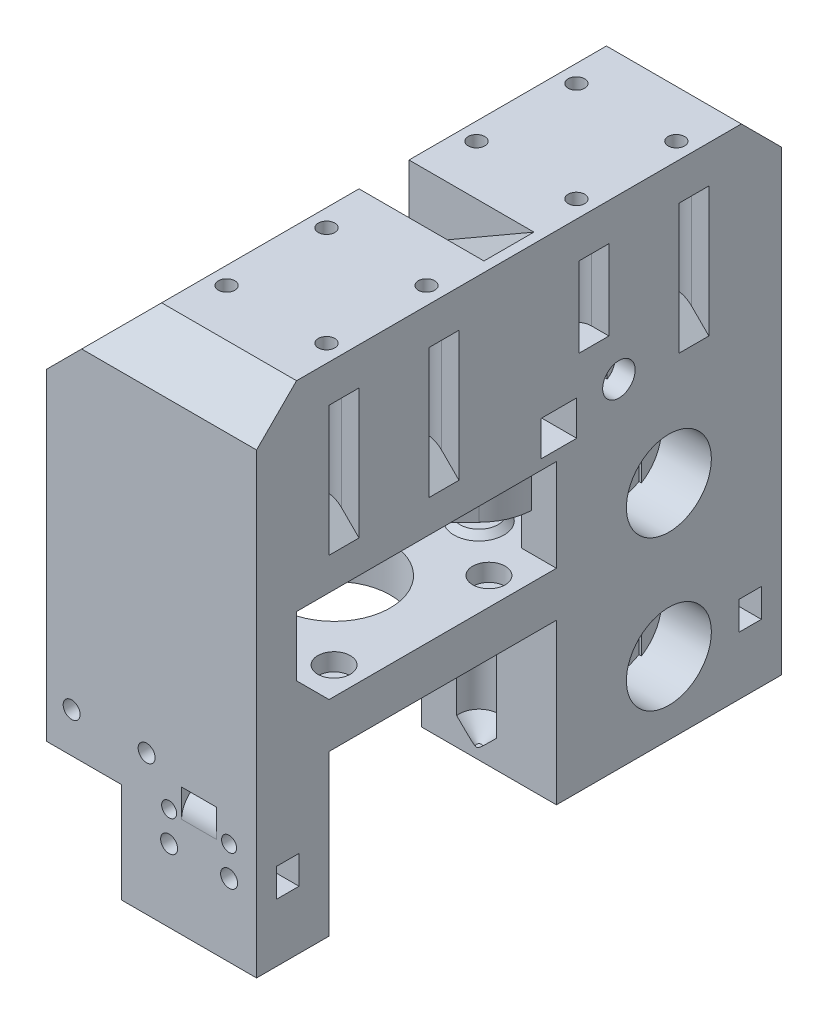
SolidWorks part; units mm, degrees
material "3D printed plastic"
ref_plane "Front Plane" through (0, 0, 0) normal (0, 0, 1) x (1, 0, 0)
ref_plane "Top Plane" through (0, 0, 0) normal (0, 1, 0) x (1, 0, 0)
ref_plane "Right Plane" through (0, 0, 0) normal (1, 0, 0) x (0, 0, -1)
sketch "Sketch1" plane through (0, 0, 0) normal (0, 1, 0) x (1, 0, 0)
  line L0 (-13.5, 52.5) -> (13.5, -52.5) construction
  line L1 (-13.5, 52.5) -> (13.5, 52.5)
  line L2 (-13.5, 52.5) -> (-13.5, -52.5)
  line L3 (-13.5, -52.5) -> (13.5, -52.5)
  line L4 (13.5, 52.5) -> (13.5, -52.5)
  dimension "D1" = 27
  dimension "D2" = 105
extrude "Boss-Extrude1" add sketch "Sketch1" against normal blind 40
sketch "Sketch2" plane through (0, -40, 0) normal (0, -1, 0) x (-1, 0, 0)
  line L0 (-13.5, -52.5) -> (-13.5, 52.5) construction
  line L1 (13.5, 52.5) -> (-13.5, 52.5)
  line L2 (13.5, 52.5) -> (13.5, 45.1)
  line L3 (13.5, 7.5) -> (-13.5, 7.5)
  line L4 (-13.5, 52.5) -> (-13.5, 7.5)
  line L5 (13.5, 14.9) -> (13.5, 7.5)
  line L6 (13.5, 45.1) -> (8.5, 45.1)
  line L7 (8.5, 30) -> (13.5, 30) construction
  line L8 (13.5, 14.9) -> (8.5, 14.9)
  line L9 (8.5, 45.1) -> (8.5, 14.9)
  line L10 (13.5, 52.5) -> (13.5, -52.5) construction
  dimension "D1" = 30.2
  dimension "D2" = 22.5
  dimension "D3" = 5
  dimension "D4" = 45
extrude "Boss-Extrude2" add sketch "Sketch2" along normal blind 59.5
sketch "Sketch4" plane through (13.5, 0, 0) normal (1, 0, 0) x (0, 0, -1)
  line L0 (30, -55) -> (30, -85) construction
  line L1 (30, -85) -> (30, -99.5) construction
  line L2 (45.1, -99.5) -> (14.9, -99.5) construction
  line L3 (14.9, -40) -> (45.1, -40) construction
  circle A0 centre (30, -85) radius 4.5
  circle A1 centre (30, -55) radius 4.5
  dimension "D1" = 30
  dimension "D3" = 9
  dimension "D2" = 15
extrude "Cut-Extrude2" cut sketch "Sketch4" against normal through all
sketch "Sketch5" plane through (13.5, 0, 0) normal (1, 0, 0) x (0, 0, -1)
  circle A0 centre (30, -85) radius 8.5
  circle A1 centre (30, -55) radius 8.5
  dimension "D1" = 17
extrude "Cut-Extrude3" cut sketch "Sketch5" against normal blind 10
sketch "Sketch6" plane through (0, 0, 0) normal (0, 1, 0) x (-1, 0, 0)
  line L0 (-10, 35) -> (-10, 15) construction
  line L1 (-10, 15) -> (10, 15) construction
  line L2 (10, 15) -> (10, 35) construction
  line L3 (10, 35) -> (-10, 35) construction
  line L5 (-10, 35) -> (10, 15) construction
  line L6 (0, 25) -> (0, -25) construction
  line L7 (0, 0) -> (13.5, 0) construction
  line L8 (-10, -35) -> (10, -15) construction
  line L9 (10, -35) -> (-10, -35) construction
  line L10 (10, -15) -> (10, -35) construction
  line L11 (-10, -15) -> (10, -15) construction
  line L12 (-10, -35) -> (-10, -15) construction
  line L13 (13.5, -52.5) -> (13.5, 52.5) construction
  circle A0 centre (-10, 35) radius 1.65
  circle A1 centre (10, 35) radius 1.65
  circle A2 centre (10, 15) radius 1.65
  circle A3 centre (-10, 15) radius 1.65
  circle A4 centre (-10, -15) radius 1.65
  circle A5 centre (10, -15) radius 1.65
  circle A6 centre (10, -35) radius 1.65
  circle A7 centre (-10, -35) radius 1.65
  dimension "D1" = 20
  dimension "D2" = 3.3
  dimension "D3" = 50
  dimension "D4" = 13.5
extrude "Cut-Extrude4" cut sketch "Sketch6" against normal blind 10
ref_plane "Plane2" through (0, -67.5, 0) normal (0, -1, 0) x (-1, 0, 0)
sketch "Sketch10" plane through (0, -67.5, 0) normal (0, -1, 0) x (-1, 0, 0)
  line L0 (-8, -0.5) -> (23, -0.5) construction
  line L1 (-13.5, 52.5) -> (-13.5, 7.5) construction
  line L2 (28.5, 7.5) -> (28.5, -38)
  line L3 (28.5, -38) -> (-13.5, -38)
  line L4 (-13.5, -5.9608) -> (-13.5, -38)
  line L5 (23, -0.5) -> (23, -31.5) construction
  line L6 (23, -31.5) -> (-8, -31.5) construction
  line L7 (-8, -31.5) -> (-8, -0.5) construction
  line L8 (-8, -0.5) -> (23, -31.5) construction
  line L9 (7.5, -16) -> (28.5, -16) construction
  line L10 (13.5, 14.9) -> (13.5, 7.5)
  line L11 (13.5, 14.9) -> (-13.5, 14.9)
  line L12 (13.5, 7.5) -> (28.5, 7.5)
  line L14 (-13.5, 14.9) -> (-13.5, -5.9608)
  circle A0 centre (7.5, -16) radius 11.25
  circle A1 centre (23, -0.5) radius 1.75 construction
  circle A2 centre (23, -31.5) radius 1.75
  circle A3 centre (-8, -31.5) radius 1.75
  circle A4 centre (-8, -0.5) radius 1.75
  dimension "D1" = 31
  dimension "D2" = 22.5
  dimension "D3" = 3.5
  dimension "D4" = 22
  dimension "D5" = 21
  dimension "D6" = 42
  dimension "D7" = 23.5
extrude "Boss-Extrude3" add sketch "Sketch10" against normal blind 9
sketch "Sketch11" plane through (13.5, 0, 0) normal (1, 0, 0) x (0, 0, -1)
  line L0 (52.5, -99.5) -> (7.5, -99.5) construction
  line L1 (-38, -99.5) -> (-52.5, -99.5)
  line L2 (-38, -99.5) -> (-38, -58.5)
  line L3 (-44.5, 0) -> (-52.5, 0)
  line L4 (-52.5, -99.5) -> (-52.5, 0)
  line L6 (-38, -58.5) -> (-44.5, -52)
  line L8 (-44.5, -52) -> (-44.5, 0)
  dimension "D1" = 8
  dimension "D2" = 45
extrude "Boss-Extrude4" add sketch "Sketch11" against normal up to surface (42 mm away) up to face at (-28.5, -63, 15.25)
sketch "Sketch24" plane through (0, -58.5, 0) normal (0, 1, 0) x (-1, 0, 0)
  circle A0 centre (21.5, 6.5) radius 2.1
  circle A1 centre (2.5, -8) radius 2.1
  circle A2 centre (7.5, 16) radius 11.25 construction
  dimension "D1" = 4.2
  dimension "D2" = 9.5
  dimension "D4" = 14
  dimension "D5" = 5
  dimension "D3" = 24
extrude "Cut-Extrude16" cut sketch "Sketch24" against normal blind 15
sketch "Sketch26" plane through (0, -58.5, 0) normal (0, 1, 0) x (-1, 0, 0)
  line L0 (2.5, -17) -> (13.5, -17)
  line L1 (13.5, -17) -> (13.5, 1)
  line L2 (13.5, 1) -> (2.5, 1)
  line L4 (13.5, -52.5) -> (13.5, 44.5) construction
  arc A0 (2.5, 1) -> (2.5, -17) centre (2.5, -8) ccw
  dimension "D1" = 18
extrude "Cut-Extrude18" cut sketch "Sketch26" along normal blind 7.5
sketch "Sketch27" plane through (0, -67.5, 0) normal (0, -1, 0) x (-1, 0, 0)
  circle A0 centre (2.5, 8) radius 4
  circle A1 centre (21.5, -6.5) radius 4
  dimension "D1" = 8
extrude "Cut-Extrude19" cut sketch "Sketch27" against normal blind 4.5 and the other way blind 30
sketch "Sketch28" plane through (0, -51, 0) normal (0, -1, 0) x (-1, 0, 0)
  line L0 (21.5, -12) -> (9.0147, -12)
  line L1 (5.4792, -10.5355) -> (-5.2782, 0.2218)
  line L2 (21.5, -1) -> (14.5, -1)
  line L3 (13.5, 0) -> (13.5, 8)
  line L4 (13.5, 14.9) -> (13.5, 7.5) construction
  line L5 (11.0668, 14.9) -> (8.5, 14.9)
  line L6 (8.5, 14.9) -> (8.5, 17.2195)
  line L8 (8.5, 14.9) -> (13.5, 14.9) construction
  arc A0 (13.5, 8) -> (11.0668, 14.9) centre (2.5, 8) ccw
  arc A1 (8.5, 17.2195) -> (-5.2782, 0.2218) centre (2.5, 8) ccw
  arc A2 (21.5, -12) -> (21.5, -1) centre (21.5, -6.5) ccw
  arc A3 (9.0147, -12) -> (5.4792, -10.5355) centre (9.0147, -7) cw
  arc A4 (14.5, -1) -> (13.5, 0) centre (14.5, 0) cw
  arc A5 (2.5, 17) -> (-6.4861, 7.5) centre (2.5, 8) ccw construction
  dimension "D1" = 45
  dimension "D2" = 11
  dimension "D3" = 5
  dimension "D4" = 1
extrude "Boss-Extrude6" add sketch "Sketch28" against normal blind 20
sketch "Sketch29" plane through (0, -51, 0) normal (0, -1, 0) x (-1, 0, 0)
  circle A0 centre (2.5, 8) radius 2.1
  circle A2 centre (21.5, -6.5) radius 2.1
  circle A3 centre (21.5, -6.5) radius 2.1 construction
extrude "Cut-Extrude20" cut sketch "Sketch29" against normal blind 20
sketch "Sketch30" plane through (0, -58.5, 0) normal (0, 1, 0) x (-1, 0, 0)
  circle A0 centre (2.5, -8) radius 2.1
  circle A1 centre (2.5, -8) radius 5
  circle A2 centre (2.5, -8) radius 2.1 construction
  circle A3 centre (21.5, 6.5) radius 2.1 construction
  circle A4 centre (21.5, 6.5) radius 2.1
  circle A6 centre (21.5, 6.5) radius 5
  dimension "D1" = 10
extrude "Boss-Extrude7" add sketch "Sketch30" along normal blind 1.2
sketch "Sketch31" plane through (0, -51, 0) normal (0, -1, 0) x (-1, 0, 0)
  circle A0 centre (2.5, 8) radius 2.1
  circle A1 centre (2.5, 8) radius 5
  circle A2 centre (2.5, 8) radius 2.1 construction
  circle A3 centre (2.5, 8) radius 5 construction
  circle A4 centre (21.5, -6.5) radius 2.1
  circle A5 centre (21.5, -6.5) radius 2.1 construction
  circle A6 centre (21.5, -6.5) radius 5
extrude "Boss-Extrude8" add sketch "Sketch31" along normal blind 1.2
chamfer "Chamfer6" distance 1.2 angle 45 4 edges at (-21.5, -57.3, 11.5) (-2.5, -57.3, -3) (-2.5, -52.2, -13) (-21.5, -52.2, 1.5)
sketch "Sketch32" plane through (0, -31, 0) normal (0, 1, 0) x (-1, 0, 0)
  line L1 (25.5992, 6.5) -> (23.5496, 10.05)
  line L2 (23.5496, 10.05) -> (19.4504, 10.05)
  line L3 (19.4504, 10.05) -> (17.4008, 6.5)
  line L4 (17.4008, 6.5) -> (19.4504, 2.95)
  line L5 (19.4504, 2.95) -> (23.5496, 2.95)
  line L6 (23.5496, 2.95) -> (25.5992, 6.5)
  line L7 (6.5992, -8) -> (4.5496, -4.45)
  line L8 (4.5496, -4.45) -> (0.4504, -4.45)
  line L9 (0.4504, -4.45) -> (-1.5992, -8)
  line L10 (-1.5992, -8) -> (0.4504, -11.55)
  line L11 (0.4504, -11.55) -> (4.5496, -11.55)
  line L12 (4.5496, -11.55) -> (6.5992, -8)
  circle A0 centre (21.5, 6.5) radius 3.55 construction
  circle A1 centre (2.5, -8) radius 3.55 construction
  dimension "D1" = 7.1
extrude "Cut-Extrude21" cut sketch "Sketch32" against normal blind 7
sketch "Sketch34" plane through (0, -58.5, 0) normal (0, 1, 0) x (-1, 0, 0)
  circle A0 centre (-8, 31.5) radius 3.25
  circle A1 centre (23, 31.5) radius 3.25
  circle A2 centre (-8, 0.5) radius 3.25
  circle A3 centre (-8, 0.5) radius 1.75 construction
  dimension "D1" = 6.5
extrude "Cut-Extrude23" cut sketch "Sketch34" against normal blind 3.5
sketch "Sketch35" plane through (0, -38, 0) normal (0, 1, 0) x (1, 0, 0)
  line L0 (-0.4504, 11.55) -> (13.5, 11.55)
  line L1 (13.5, 11.55) -> (13.5, 4.45)
  line L2 (13.5, 4.45) -> (-0.4504, 4.45)
  line L3 (-0.4504, 4.45) -> (-0.4504, 11.55)
  line L4 (13.5, 7.5) -> (13.5, -38) construction
extrude "Cut-Extrude24" cut sketch "Sketch35" along normal up to surface (7 mm away) up to face at (-2.5, -31, -8)
chamfer "Chamfer7" distance 3.5 angle 45 1 edges at (-2.5, -97.5, -12)
chamfer "Chamfer8" distance 15 angle 45 1 edges at (-28.5, 0, 48.5)
chamfer "Chamfer10" distance 12 angle 45 1 edges at (-13.5, -31, 6)
sketch "Sketch36" plane through (0, 0, 0) normal (0, 1, 0) x (1, 0, 0)
  line L0 (-10, 35) -> (-13.5, 35) construction
  line L1 (-13.5, 52.5) -> (-13.5, -44.5) construction
  line L2 (-10, 32) -> (-13.5, 32)
  line L3 (-10, 38) -> (-13.5, 38)
  line L4 (-10, 15) -> (-13.5, 15) construction
  line L5 (-10, 12) -> (-13.5, 12)
  line L6 (-10, 18) -> (-13.5, 18)
  line L7 (-10, -15) -> (-13.5, -15) construction
  line L8 (-10, -18) -> (-13.5, -18)
  line L9 (-10, -12) -> (-13.5, -12)
  line L10 (-10, -35) -> (-13.5, -35) construction
  line L11 (-10, -38) -> (-13.5, -38)
  line L12 (-10, -32) -> (-13.5, -32)
  line L13 (10, 35) -> (13.5, 35) construction
  line L14 (13.5, -52.5) -> (13.5, 52.5) construction
  line L15 (10, 38) -> (13.5, 38)
  line L16 (10, 32) -> (13.5, 32)
  line L17 (10, 15) -> (13.5, 15) construction
  line L18 (10, 18) -> (13.5, 18)
  line L19 (10, 12) -> (13.5, 12)
  line L20 (10, -15) -> (13.5, -15) construction
  line L21 (10, -12) -> (13.5, -12)
  line L22 (10, -18) -> (13.5, -18)
  line L23 (10, -35) -> (13.5, -35) construction
  line L24 (10, -32) -> (13.5, -32)
  line L25 (10, -38) -> (13.5, -38)
  arc A0 (-10, 32) -> (-10, 38) centre (-10, 35) ccw
  arc A1 (-13.5, 38) -> (-13.5, 32) centre (-13.5, 35) ccw
  arc A2 (-10, 12) -> (-10, 18) centre (-10, 15) ccw
  arc A3 (-13.5, 18) -> (-13.5, 12) centre (-13.5, 15) ccw
  arc A4 (-10, -18) -> (-10, -12) centre (-10, -15) ccw
  arc A5 (-13.5, -12) -> (-13.5, -18) centre (-13.5, -15) ccw
  arc A6 (-10, -38) -> (-10, -32) centre (-10, -35) ccw
  arc A7 (-13.5, -32) -> (-13.5, -38) centre (-13.5, -35) ccw
  circle A8 centre (-10, -15) radius 1.65 construction
  arc A9 (10, 38) -> (10, 32) centre (10, 35) ccw
  arc A10 (13.5, 32) -> (13.5, 38) centre (13.5, 35) ccw
  arc A11 (10, 18) -> (10, 12) centre (10, 15) ccw
  arc A12 (13.5, 12) -> (13.5, 18) centre (13.5, 15) ccw
  arc A13 (10, -12) -> (10, -18) centre (10, -15) ccw
  arc A14 (13.5, -18) -> (13.5, -12) centre (13.5, -15) ccw
  arc A15 (10, -32) -> (10, -38) centre (10, -35) ccw
  arc A16 (13.5, -38) -> (13.5, -32) centre (13.5, -35) ccw
  point P5 (-11.75, 35)
  point P10 (-11.75, 15)
  point P18 (-11.75, -15)
  point P25 (-11.75, -35)
  point P40 (11.75, 35)
  point P45 (11.75, 15)
  point P53 (11.75, -15)
  point P61 (11.75, -35)
  dimension "D1" = 6
extrude "Cut-Extrude25" cut sketch "Sketch36" against normal blind 16 from offset 7.5 offset against normal yes
chamfer "Chamfer12" distance 10 angle 45 6 edges at (-13.5, -23.5, -35) (-13.5, -23.5, 15) (-13.5, -23.5, 35) (13.5, -23.5, -35) (13.5, -23.5, 15) (13.5, -23.5, 35)
sketch "Sketch37" plane through (-13.5, 0, 0) normal (-1, 0, 0) x (0, 0, 1)
  line L1 (-23.8, -40) -> (-16.2, -40)
  line L2 (-23.8, -40) -> (-23.8, -24)
  line L3 (-23.8, -24) -> (-16.2, -24)
  line L4 (-16.2, -40) -> (-16.2, -24)
  line L5 (-20, -40) -> (-20, -55) construction
  line L6 (-30, -55) -> (-20, -55) construction
  line L7 (-23.8, -32) -> (-25.8998, -32) construction
  circle A0 centre (-30, -55) radius 4.5 construction
  dimension "D1" = 10
  dimension "D2" = 7.6
  dimension "D3" = 16
  dimension "D4" = 23
extrude "Cut-Extrude26" cut sketch "Sketch37" against normal blind 20
sketch "Sketch38" plane through (6.5, 0, 0) normal (-1, 0, 0) x (0, 0, 1)
  line L0 (-23.8, -24) -> (-16.2, -40) construction
  circle A0 centre (-20, -32) radius 1.65
  dimension "D1" = 3.3
extrude "Cut-Extrude27" cut sketch "Sketch38" against normal through all
sketch "Sketch39" plane through (13.5, 0, 0) normal (1, 0, 0) x (0, 0, -1)
  circle A0 centre (20, -32) radius 3.25
  circle A1 centre (20, -32) radius 1.65 construction
  dimension "D1" = 6.5
extrude "Cut-Extrude28" cut sketch "Sketch39" against normal blind 4
sketch "Sketch40" plane through (13.5, 0, 0) normal (1, 0, 0) x (0, 0, -1)
  line L0 (52.5, -99.5) -> (50.5, -99.5)
  line L1 (52.5, -99.5) -> (7.5, -99.5) construction
  line L2 (42.5, -91.5) -> (42.5, -79.5)
  line L3 (52.5, -99.5) -> (52.5, 0) construction
  arc A0 (50.5, -99.5) -> (42.5, -91.5) centre (50.5, -91.5) cw
  arc A1 (42.5, -79.5) -> (52.5, -79.5) centre (47.5, -79.5) cw
  dimension "D1" = 10
  dimension "D3" = 20
  dimension "D2" = 2
sketch "Sketch41" plane through (0, 0, -52.5) normal (0, 0, -1) x (-1, 0, 0)
  line L0 (13.5, -99.5) -> (-13.5, -99.5) construction
  line L1 (-5.5, -99.5) -> (1.5, -99.5)
  line L2 (-5.5, -99.5) -> (-5.5, -102)
  line L3 (-5.5, -102) -> (1.5, -102)
  line L4 (1.5, -99.5) -> (1.5, -102)
  line L5 (-2, -99.5) -> (-2, -97.2368) construction
  line L6 (-13.5, -91.5) -> (-13.5, -99.5) construction
  dimension "D1" = 11.5
  dimension "D2" = 7
  dimension "D3" = 2.5
sweep "Cut-Sweep1" cut profiles "Sketch41" path "Sketch40"
hole_wizard "M3 Clearance Hole1" positions "Sketch43" profile "Sketch42" hole size "M3" standard "DIN"
sketch "Sketch43" plane through (0, 0, -52.5) normal (0, 0, -1) x (-1, 0, 0)
  line L1 (4, -85) -> (-8, -85) construction
  line L3 (-2, -73.9098) -> (-2, -85) construction
  line L4 (-5.5, -73.9098) -> (1.5, -73.9098) construction
  line L7 (-8, -85) -> (-13.5, -85) construction
  line L8 (-13.5, -99.5) -> (-13.5, 0) construction
  line L10 (-13.5, -76.5) -> (-13.5, -93.5) construction
  point P0 (-8, -85)
  point P2 (4, -85)
  dimension "D1" = 12
sketch "Sketch42" plane through (8, -85, -52.5) normal (1, 0, 0) x (0, 1, 0)
  line L0 (0, 0) -> (0, 13.0215)
  line L1 (0, 13.0215) -> (1.7, 12)
  line L2 (1.7, 12) -> (1.7, 0)
  line L5 (1.7, 0) -> (0, 0)
  line L10 (0, 13.0215) -> (-1.7, 12) construction
  line L11 (0, -6.35) -> (0, 107.95) construction
  dimension "Hole Dia." = 3.4
  dimension "Hole Depth" = 12
  dimension "Drill Angle" = 118
sketch "Sketch44" plane through (0, 0, -52.5) normal (0, 0, -1) x (-1, 0, 0)
  line L0 (5.6454, -82.15) -> (28.5, -82.15)
  line L1 (-11.2909, -85) -> (-9.6454, -87.85) construction
  line L2 (-9.6454, -87.85) -> (-6.3546, -87.85)
  line L3 (-6.3546, -87.85) -> (-4.7091, -85)
  line L4 (-4.7091, -85) -> (-6.3546, -82.15)
  line L5 (-6.3546, -82.15) -> (-9.6454, -82.15)
  line L6 (-9.6454, -82.15) -> (-11.2909, -85) construction
  line L7 (7.2909, -85) -> (5.6454, -82.15) construction
  line L8 (5.6454, -82.15) -> (2.3546, -82.15)
  line L9 (2.3546, -82.15) -> (0.7091, -85)
  line L10 (0.7091, -85) -> (2.3546, -87.85)
  line L11 (2.3546, -87.85) -> (5.6454, -87.85)
  line L12 (5.6454, -87.85) -> (7.2909, -85) construction
  line L14 (28.5, -82.15) -> (28.5, -87.85)
  line L15 (28.5, -87.85) -> (5.6454, -87.85)
  line L16 (-9.6454, -82.15) -> (-13.5, -82.15)
  line L17 (-13.5, -99.5) -> (-13.5, 0) construction
  line L18 (-13.5, -82.15) -> (-13.5, -87.85)
  line L19 (-13.5, -87.85) -> (-9.6454, -87.85)
  line L20 (28.5, -99.5) -> (28.5, -67.5) construction
  circle A0 centre (-8, -85) radius 2.85 construction
  circle A1 centre (4, -85) radius 2.85 construction
  dimension "D1" = 5.7
extrude "Cut-Extrude29" cut sketch "Sketch44" against normal blind 4.5 from offset 4 offset against normal yes
ref_plane "Plane3" through (0, 0, 0) normal (0, 0, -1) x (-1, 0, 0)
sketch "Sketch47" plane through (0, 0, -52.5) normal (0, 0, -1) x (-1, 0, 0)
  line L0 (4, -79) -> (-8, -79) construction
  line L1 (-8, -85) -> (4, -85) construction
  line L2 (-2, -79) -> (-2, -85) construction
  circle A0 centre (-8, -79) radius 1.5
  circle A1 centre (4, -79) radius 1.5
  dimension "D1" = 3
  dimension "D2" = 4.5
  dimension "D3" = 12
extrude "Cut-Extrude32" cut sketch "Sketch47" against normal blind 8
mirror "Mirror1" about plane through (0, 0, 0) normal (0, 0, -1) of "Cut-Extrude32", "M3 Clearance Hole1", "Cut-Extrude29", "Cut-Sweep1"
sketch "Sketch45" plane through (0, 0, 52.5) normal (0, 0, 1) x (1, 0, 0)
  line L0 (-28.5, -79.5) -> (-13.5, -79.5)
  line L1 (-28.5, -15) -> (-28.5, -99.5) construction
  line L2 (-13.5, -79.5) -> (-13.5, -99.5)
  line L3 (-28.5, -99.5) -> (13.5, -99.5) construction
  line L4 (-13.5, -99.5) -> (-28.5, -99.5)
  line L5 (-28.5, -99.5) -> (-28.5, -79.5)
  line L8 (-13.5, -99.5) -> (-13.5, 0) construction
  dimension "D2" = 20
extrude "Cut-Extrude30" cut sketch "Sketch45" against normal up to next
sketch "Sketch46" plane through (0, 0, 0) normal (0, 0, -1) x (-1, 0, 0)
  line L0 (-11.5, 0) -> (13.5, -14.4338)
  line L1 (13.5, 0) -> (13.5, -40) construction
  line L2 (13.5, -14.4338) -> (13.5, 0)
  line L3 (-13.5, 0) -> (13.5, 0) construction
  line L4 (13.5, 0) -> (-11.5, 0)
  line L5 (-13.5, -99.5) -> (-13.5, 0) construction
  dimension "D1" = 30
  dimension "D2" = 2
extrude "Cut-Extrude31" cut sketch "Sketch46" against normal mid plane 10
chamfer "Chamfer13" distance 8 angle 45 2 edges at (0, 0, 52.5) (0, 0, -52.5)
chamfer "Chamfer14" distance 6 angle 45 1 edges at (-13.5, -20, 44.5)
sketch "Sketch48" plane through (-8.5, 0, 0) normal (-1, 0, 0) x (0, 0, 1)
  line L0 (-45.1, -82.15) -> (-45.1, -40) construction
  line L1 (-45.1, -51) -> (-43.1, -51)
  line L2 (-45.1, -51) -> (-45.1, -59)
  line L3 (-45.1, -59) -> (-43.1, -59)
  line L4 (-43.1, -51) -> (-43.1, -59)
  line L5 (-45.1, -40) -> (-23.8, -40) construction
  line L6 (-34, -40) -> (-26, -40)
  line L7 (-34, -40) -> (-34, -42)
  line L8 (-34, -42) -> (-26, -42)
  line L9 (-26, -40) -> (-26, -42)
  line L10 (-30, -42) -> (-30, -55) construction
  line L11 (-30, -55) -> (-43.1, -55) construction
  dimension "D1" = 8
  dimension "D2" = 2
extrude "Boss-Extrude9" add sketch "Sketch48" along normal up to surface (5 mm away) up to face at (-13.5, -38.5609, -13.8017)
chamfer "Chamfer15" distance 6 angle 45 1 edges at (-28.5, -63, -7.5)
sketch "Sketch49" plane through (-13.5, 0, 0) normal (-1, 0, 0) x (0, 0, 1)
  line L0 (-52.5, -99.5) -> (-52.5, -8) construction
  line L1 (-52.5, -9.5) -> (-39, -9.5)
  line L2 (-52.5, -9.5) -> (-52.5, -30.5)
  line L3 (-52.5, -30.5) -> (-39, -30.5)
  line L4 (-39, -9.5) -> (-39, -30.5)
  line L5 (-52.5, -20) -> (-39, -20) construction
  line L6 (-44.5, 0) -> (-5, 0) construction
  dimension "D1" = 21
  dimension "D2" = 13.5
  dimension "D3" = 20
extrude "Cut-Extrude33" cut sketch "Sketch49" against normal blind 0.5
sketch "Sketch50" plane through (-13, 0, 0) normal (-1, 0, 0) x (0, 0, 1)
  line L0 (-46.8, -24.3) -> (-46.8, -14.8) construction
  line L1 (-46.8, -19.55) -> (-48.1147, -19.55) construction
  line L2 (-52.5, -9.5) -> (-52.5, -30.5) construction
  line L3 (-39, -9.5) -> (-52.5, -9.5) construction
  circle A0 centre (-46.8, -14.8) radius 0.85
  circle A1 centre (-46.8, -24.3) radius 0.85
  dimension "D1" = 1.7
  dimension "D4" = 5.3
  dimension "D2" = 9.5
  dimension "D3" = 5.7
extrude "Cut-Extrude34" cut sketch "Sketch50" against normal blind 10
sketch "Sketch51" plane through (-13.5, 0, 0) normal (-1, 0, 0) x (0, 0, 1)
  line L0 (-3.1, -31.6) -> (-3.1, -41.6) construction
  circle A0 centre (-3.1, -31.6) radius 1.25
  circle A1 centre (-3.1, -41.6) radius 1.25
  circle A2 centre (-30, -55) radius 4.5 construction
  dimension "D1" = 10
  dimension "D2" = 2.5
  dimension "D3" = 26.9
  dimension "D4" = 13.4
extrude "Cut-Extrude35" cut sketch "Sketch51" against normal blind 15
sketch "Sketch52" plane through (0, 0, 52.5) normal (0, 0, 1) x (1, 0, 0)
  line L0 (-8.5, -71.5) -> (-23.5, -71.5) construction
  line L3 (-23.5, -71.5) -> (-28.5, -71.5) construction
  line L4 (-28.5, -15) -> (-28.5, -79.5) construction
  line L6 (13.5, -67.5) -> (-28.5, -67.5) construction
  circle A0 centre (-23.5, -71.5) radius 1.7
  circle A1 centre (-8.5, -71.5) radius 1.7
  point P4 (-7.5, -67.5)
  dimension "D1" = 3.4
  dimension "D2" = 4
  dimension "D3" = 15
  dimension "D4" = 5
extrude "Cut-Extrude36" cut sketch "Sketch52" against normal up to next
sketch "Sketch53" plane through (0, 0, 38) normal (0, 0, -1) x (-1, 0, 0)
  line L1 (11.7909, -71.5) -> (10.1454, -68.65)
  line L2 (10.1454, -68.65) -> (6.8546, -68.65)
  line L3 (6.8546, -68.65) -> (5.2091, -71.5)
  line L4 (5.2091, -71.5) -> (6.8546, -74.35)
  line L5 (6.8546, -74.35) -> (10.1454, -74.35)
  line L6 (10.1454, -74.35) -> (11.7909, -71.5)
  line L7 (20.2091, -71.5) -> (21.8546, -74.35)
  line L8 (21.8546, -74.35) -> (25.1454, -74.35)
  line L9 (25.1454, -74.35) -> (26.7909, -71.5)
  line L10 (26.7909, -71.5) -> (25.1454, -68.65)
  line L11 (25.1454, -68.65) -> (21.8546, -68.65)
  line L12 (21.8546, -68.65) -> (20.2091, -71.5)
  circle A0 centre (8.5, -71.5) radius 2.85 construction
  circle A1 centre (23.5, -71.5) radius 2.85 construction
  dimension "D1" = 5.7
extrude "Cut-Extrude37" cut sketch "Sketch53" against normal blind 10
ref_plane "Plane4" through (0, 0, 25) normal (0, 0, 1) x (1, 0, 0)
sketch "Sketch54" plane through (0, 0, 25) normal (0, 0, 1) x (1, 0, 0)
  line L0 (-9.5, -10.5) -> (-9.5, -9.5)
  line L2 (-13.5, -30.5) -> (-13.5, -9.5) construction
  line L3 (-13.5, -14.5) -> (-13.5, -16.5)
  line L4 (-13.5, -19) -> (-13.5, -51) construction
  line L5 (-7.5, -10.5) -> (-7.5, -9.5)
  line L6 (-13.5, -3.5) -> (-13.5, -5.5)
  line L7 (-13.5, -40) -> (-13.5, 0) construction
  line L8 (-7.5, -10) -> (-12.6948, -10) construction
  line L9 (-13.5, 0) -> (11.5, 0) construction
  arc A0 (-9.5, -9.5) -> (-13.5, -5.5) centre (-13.5, -9.5) ccw
  arc A1 (-9.5, -10.5) -> (-13.5, -14.5) centre (-13.5, -10.5) cw
  arc A2 (-13.5, -16.5) -> (-7.5, -10.5) centre (-13.5, -10.5) ccw
  arc A3 (-7.5, -9.5) -> (-13.5, -3.5) centre (-13.5, -9.5) ccw
  dimension "D1" = 2
  dimension "D2" = 1
  dimension "D3" = 4
  dimension "D4" = 10
extrude "Cut-Extrude38" cut sketch "Sketch54" against normal mid plane 6
mirror "Mirror2" about plane through (0, 0, 0) normal (0, 0, 1) of "Cut-Extrude38"
sketch "Sketch55" plane through (0, -51, 0) normal (0, -1, 0) x (1, 0, 0)
  circle A0 centre (-7.5, 16) radius 10
  dimension "D1" = 20
extrude "Cut-Extrude39" cut sketch "Sketch55" against normal blind 5
sketch "Sketch57" plane through (-28.5, 0, 0) normal (-1, 0, 0) x (0, 0, 1)
  line L0 (14.5, -60) -> (14.5, -58.5)
  line L1 (14.5, -58.5) -> (17.5, -58.5)
  line L2 (17.5, -58.5) -> (17.5, -60)
  line L3 (38, -58.5) -> (-1.5, -58.5) construction
  line L4 (16, -60) -> (16, -67.5) construction
  line L5 (38, -67.5) -> (-1.5, -67.5) construction
  line L7 (4.75, -67.5) -> (27.25, -67.5) construction
  arc A0 (14.5, -60) -> (17.5, -60) centre (16, -60) ccw
  dimension "D1" = 3
  dimension "D2" = 1.5
extrude "Cut-Extrude40" cut sketch "Sketch57" against normal up to next
sketch "Sketch58" plane through (3.5, 0, 0) normal (1, 0, 0) x (0, 0, -1)
  line L0 (25.5, -47.7889) -> (25.5, -62.2111)
  line L1 (34.5, -62.2111) -> (34.5, -47.7889)
  line L2 (25.5, -77.7889) -> (25.5, -92.2111)
  line L3 (34.5, -92.2111) -> (34.5, -77.7889)
  arc A0 (34.5, -47.7889) -> (25.5, -47.7889) centre (30, -55) ccw
  circle A1 centre (30, -55) radius 8.5 construction
  arc A2 (25.5, -62.2111) -> (34.5, -62.2111) centre (30, -55) ccw
  circle A3 centre (30, -55) radius 4.5 construction
  arc A4 (34.5, -77.7889) -> (25.5, -77.7889) centre (30, -85) ccw
  arc A5 (25.5, -92.2111) -> (34.5, -92.2111) centre (30, -85) ccw
  dimension "D1" = 2
extrude "Cut-Extrude41" cut sketch "Sketch58" against normal blind 0.5
sketch "Sketch59" plane through (9.5, 0, 0) normal (1, 0, 0) x (0, 0, -1)
  line L0 (18.35, -29.2) -> (18.35, -34.8)
  line L1 (21.65, -34.8) -> (21.65, -29.2)
  arc A0 (21.65, -29.2) -> (18.35, -29.2) centre (20, -32) ccw
  circle A1 centre (20, -32) radius 3.25 construction
  arc A2 (18.35, -34.8) -> (21.65, -34.8) centre (20, -32) ccw
  circle A3 centre (20, -32) radius 1.65 construction
extrude "Cut-Extrude42" cut sketch "Sketch59" against normal blind 0.5
